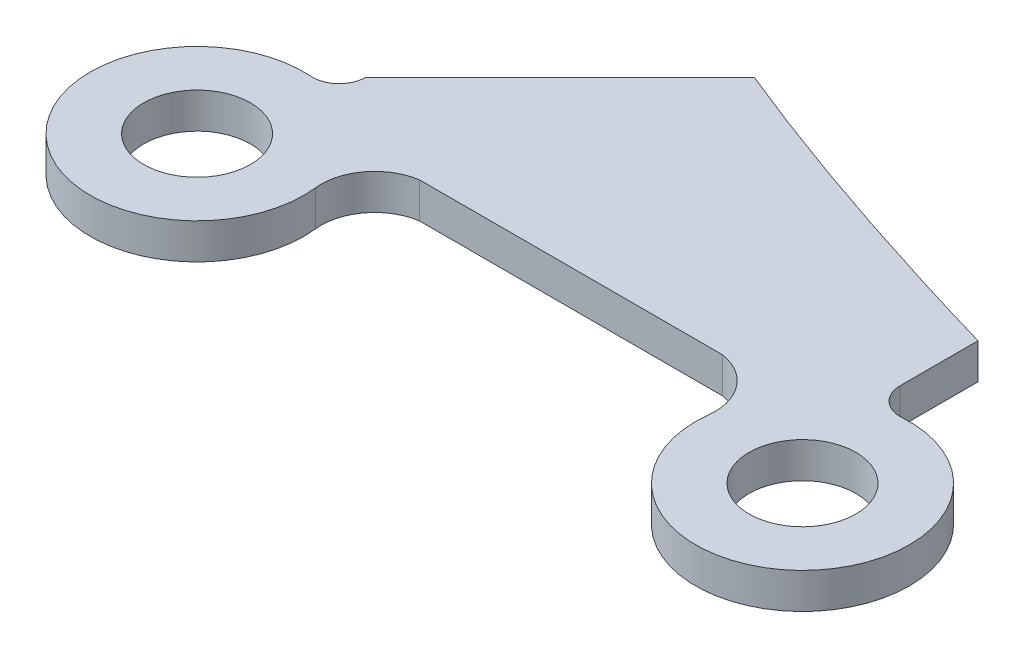
SolidWorks part; units mm, degrees
material "1.0553 (S355J0)"
ref_plane "Płaszczyzna XY" through (0, 0, 0) normal (0, 0, 1) x (1, 0, 0)
ref_plane "Płaszczyzna XZ" through (0, 0, 0) normal (0, 1, 0) x (1, 0, 0)
ref_plane "Płaszczyzna YZ" through (0, 0, 0) normal (1, 0, 0) x (0, 0, -1)
sketch "Szkic1" plane through (0, -334.4398, 0) normal (0, -1, 0) x (1, 0, 0)
  line L0 (1005, 430.7999) -> (1015.9038, 419.8961)
  line L1 (1035, 430.7128) -> (1035, 426.4272)
  line L8 (1028.5, 434.2832) -> (1011.5, 434.2832)
  line L9 (1005, 430.7999) -> (1005, 430.7128)
  line L13 (1005, 430.7128) -> (1035, 430.7128)
  line L14 (1035, 430.7128) -> (1035, 430.7999)
  line L15 (1028.5, 434.2832) -> (1011.5, 434.2832)
  line L16 (1005, 430.7999) -> (1005, 430.7128)
  line L17 (1005, 430.7128) -> (1005.0871, 430.7128)
  line L18 (1035, 430.7128) -> (1035, 430.7999)
  circle A7 centre (1003, 438.2832) radius 3 construction
  circle A8 centre (1003, 438.2832) radius 3
  circle A9 centre (1037, 438.2832) radius 3 construction
  circle A10 centre (1037, 438.2832) radius 3
  arc A13 (1008.9604, 437.5949) -> (1011.5, 434.2832) centre (1011.9406, 437.2507) ccw
  arc A14 (1008.9604, 437.5949) -> (1003.4, 432.2966) centre (1003, 438.2832) ccw
  arc A15 (1005, 430.7999) -> (1003.4, 432.2966) centre (1003.5, 430.7999) ccw
  arc A16 (1036.6, 432.2966) -> (1035, 430.7999) centre (1036.5, 430.7999) ccw
  arc A17 (1036.6, 432.2966) -> (1031.0396, 437.5949) centre (1037, 438.2832) ccw
  arc A18 (1028.5, 434.2832) -> (1031.0396, 437.5949) centre (1028.0594, 437.2507) ccw
  arc A19 (1008.9604, 437.5949) -> (1011.5, 434.2832) centre (1011.9406, 437.2507) ccw
  arc A20 (1008.9604, 437.5949) -> (1003.4, 432.2966) centre (1003, 438.2832) ccw
  arc A21 (1005, 430.7999) -> (1003.4, 432.2966) centre (1003.5, 430.7999) ccw
  arc A22 (1036.6, 432.2966) -> (1035, 430.7999) centre (1036.5, 430.7999) ccw
  arc A23 (1036.6, 432.2966) -> (1031.0396, 437.5949) centre (1037, 438.2832) ccw
  arc A24 (1028.5, 434.2832) -> (1031.0396, 437.5949) centre (1028.0594, 437.2507) ccw
  spline S0 degree 3 poles (999.668, 407.9697) (994.837, 432.4985) (1126.5885, 458.4475) (1131.4195, 433.9187) (1136.2506, 409.3899) (1004.4991, 383.4409) (999.668, 407.9697) (994.837, 432.4985) (1126.5885, 458.4475) knots -0.5 0 0 0 0.5 0.5 0.5 1 1 1 1.5 1.5 1.5 weights 1 0.333333 0.333333 1 0.333333 0.333333 1 0.333333 0.333333 only from (999.668, 407.9697) to (999.668, 407.9697)
  spline S1 degree 3 poles (1015.9038, 419.8961) (1021.1857, 422.0665) (1027.589, 424.2717) (1035, 426.4272) knots 0.141935 0.141935 0.141935 0.141935 0.193423 0.193423 0.193423 0.193423 weights 0.593425 0.563749 0.541144 0.525607
  dimension "D1" = 0
  dimension "D2" = 135
extrude "Dodanie-wyciągnięcie1" add sketch "Szkic1" along normal blind 2 contours L0 S1 L1 L18 A22 A23 A24 L15 A19 A20 A21 | A8 | A10
ref_plane "Płaszczyzna1" through (0, -334.4398, 0) normal (0, -1, 0) x (-1, 0, 0)
